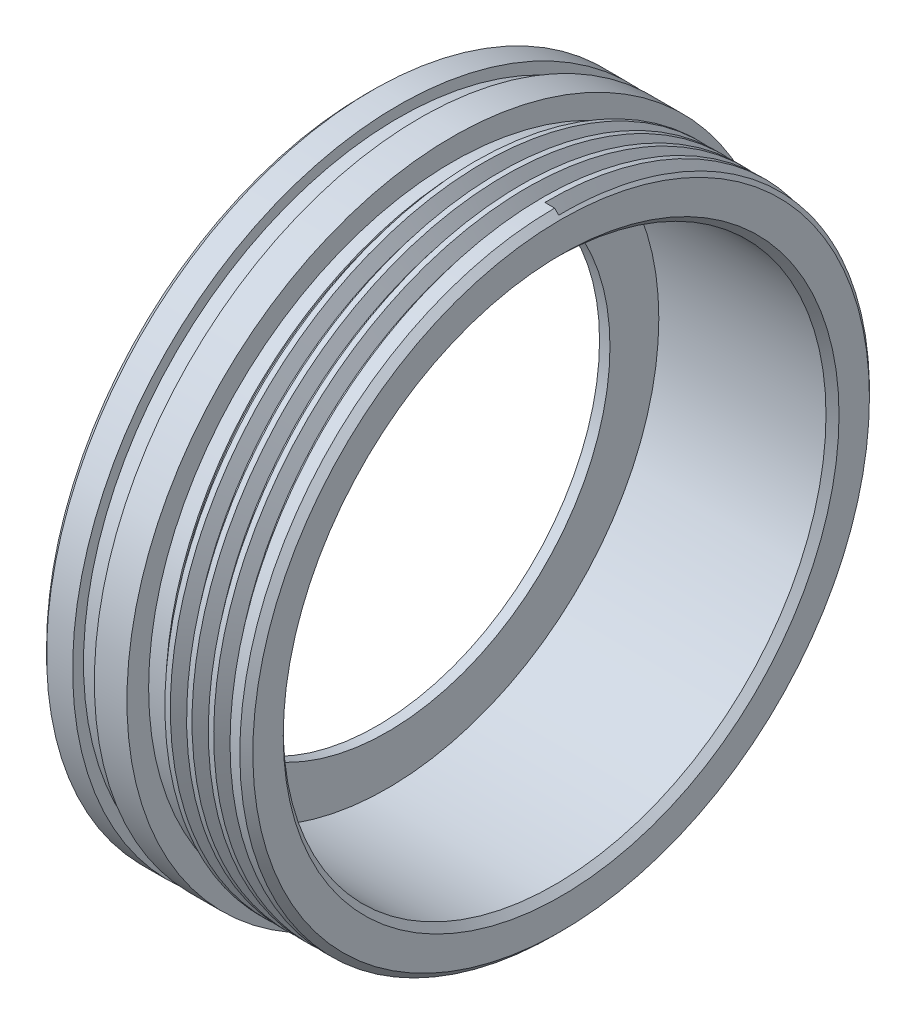
SolidWorks part; units mm, degrees
material "3.1325 (EN-AW 2017A)"
ref_plane "Front Plane" through (0, 0, 0) normal (0, 0, 1) x (1, 0, 0)
ref_plane "Top Plane" through (0, 0, 0) normal (0, 1, 0) x (1, 0, 0)
ref_plane "Right Plane" through (0, 0, 0) normal (1, 0, 0) x (0, 0, -1)
sketch "Sketch1" plane through (0, 0, 0) normal (0, 0, 1) x (1, 0, 0)
  line L0 (0, -11.15) -> (0, -14.7)
  line L2 (9, -14.2) -> (9, -12.8)
  line L4 (1, -12.5) -> (1, -10.25)
  line L5 (1, -10.25) -> (0.5196, -10.25)
  line L6 (35.4703, 0) -> (-35.4703, 0) construction
  line L9 (1, -12.5) -> (8.7, -12.5)
  line L10 (0, -14.7) -> (0.3, -15)
  line L11 (8.7, -14.5) -> (9, -14.2)
  line L12 (9, -12.8) -> (8.7, -12.5)
  line L13 (0.5196, -10.25) -> (0, -11.15)
  line L14 (0.3, -15) -> (1.5, -15)
  line L15 (1.5, -15) -> (1.5, -14.5)
  line L16 (1.5, -14.5) -> (2.5, -14.5)
  line L17 (2.5, -14.5) -> (2.5, -15)
  line L18 (2.5, -15) -> (4, -15)
  line L19 (4, -15) -> (4, -14)
  line L20 (4, -14) -> (5, -14)
  line L21 (5, -14) -> (5, -14.5)
  line L22 (5, -14.5) -> (8.7, -14.5)
  point P0 (0, -10.25)
  point P1 (0, -15)
  point P4 (9, -14.5)
  point P5 (9, -12.5)
  point P10 (0, 0)
  dimension "D2" = 20.5
  dimension "D3" = 9
  dimension "D4" = 8
  dimension "D5" = 0.5
  dimension "D6" = 1
  dimension "D7" = 25
  dimension "D8" = 0.9
  dimension "D9" = 30
  dimension "D13" = 5
  dimension "D14" = 1
  dimension "D15" = 0.5
  dimension "D16" = 1.5
  dimension "D17" = 30
  dimension "D18" = 29
revolve "Revolve1" add sketch "Sketch1" angle 360 about L6
cosmetic thread "Cosmetic Thread2"
thread "Thread2" pitch 1 method cut profile "Thread Profile2" start angle 90, offset 0, length 0, pitch 1, diameter 29
ref_plane "Plane2" through (9, 14.5, 0) normal (0, 0, 1) x (0, 1, 0)
sketch "Thread Profile2" plane through (9, 14.5, 0) normal (0, 0, 1) x (0, 1, 0)
  line L0 (0, 0) -> (0, 1) construction
  line L1 (0, 0.75) -> (-0.5413, 0.4375)
  line L2 (-0.5413, 0.4375) -> (-0.5413, 0.3125)
  line L3 (-0.5413, 0.3125) -> (0, 0)
  line L4 (-0.5413, 0.375) -> (0, 0.375) construction
  line L11 (0, 0.75) -> (0, 0)
  point P6 (0, 0)
  dimension "Pitch" = 1
  dimension "Profile_Angle" = 60
  dimension "Profile_Land" = 0.125
  dimension "Profile_Height" = 0.5413
